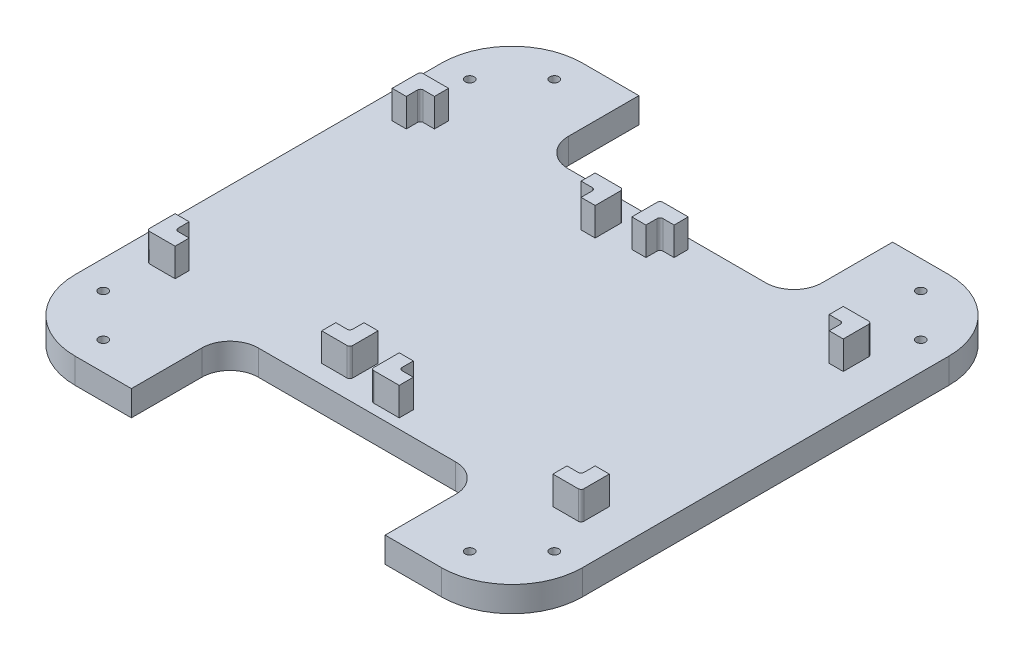
SolidWorks part; units mm, degrees
ref_plane "Front Plane" through (0, 0, 0) normal (0, 0, 1) x (1, 0, 0)
ref_plane "Top Plane" through (0, 0, 0) normal (0, 1, 0) x (1, 0, 0)
ref_plane "Right Plane" through (0, 0, 0) normal (1, 0, 0) x (0, 0, -1)
sketch "Sketch1" plane through (0, 0, 0) normal (0, 1, 0) x (1, 0, 0)
  line L1 (-65, -90) -> (65, -90)
  line L2 (-90, -65) -> (-90, 65)
  line L3 (-65, 90) -> (65, 90)
  line L4 (90, -65) -> (90, 65)
  arc A0 (-90, 65) -> (-65, 90) centre (-65, 65) cw
  arc A1 (65, 90) -> (90, 65) centre (65, 65) cw
  arc A2 (90, -65) -> (65, -90) centre (65, -65) cw
  arc A3 (-65, -90) -> (-90, -65) centre (-65, -65) cw
  point P4 (-90, 0)
  point P6 (0, 90)
  dimension "D3" = 25
  dimension "D1" = 180
  dimension "D2" = 180
extrude "Plate" add sketch "Sketch1" along normal blind 9
sketch "Sketch3" plane through (0, 9, 0) normal (0, 1, 0) x (1, 0, 0)
  line L0 (-65, 90) -> (-65, -90) construction
  line L1 (65, 90) -> (65, -90) construction
  line L2 (-90, 65) -> (90, 65) construction
  line L3 (-90, -65) -> (90, -65) construction
  circle A0 centre (-65, 80) radius 1.6
  circle A1 centre (-80, 65) radius 1.6
  circle A2 centre (80, 65) radius 1.6
  circle A3 centre (80, -65) radius 1.6
  circle A4 centre (65, 80) radius 1.6
  circle A5 centre (65, -80) radius 1.6
  circle A6 centre (-65, -80) radius 1.6
  circle A7 centre (-80, -65) radius 1.6
  dimension "D1" = 3.2
  dimension "D2" = 15
  dimension "D3" = 15
  dimension "D4" = 15
  dimension "D5" = 15
  dimension "D6" = 15
  dimension "D7" = 15
  dimension "D8" = 15
  dimension "D9" = 15
extrude "Hex Holes" cut sketch "Sketch3" against normal through all
sketch "Sketch4" plane through (0, 9, 0) normal (0, 1, 0) x (1, 0, 0)
  line L0 (90, -65) -> (90, 65) construction
  line L1 (-15, -42.5) -> (-15, 42.5) construction
  line L2 (-15, 42.5) -> (-75, 42.5) construction
  line L3 (6, 41.5) -> (6, 46.5)
  line L4 (7, 45.5) -> (70, 45.5) construction
  line L5 (7, 45.5) -> (7, -45.5) construction
  line L6 (7, -45.5) -> (70, -45.5) construction
  line L7 (70, 45.5) -> (70, -45.5) construction
  line L8 (6, 46.5) -> (11, 46.5)
  line L9 (11, 46.5) -> (11, 51.5)
  line L10 (11, 51.5) -> (1, 51.5)
  line L11 (1, 51.5) -> (1, 41.5)
  line L12 (1, 41.5) -> (6, 41.5)
  line L13 (66, 51.5) -> (76, 51.5)
  line L14 (76, 51.5) -> (76, 41.5)
  line L15 (76, 41.5) -> (71, 41.5)
  line L16 (71, 41.5) -> (71, 46.5)
  line L17 (71, 46.5) -> (66, 46.5)
  line L18 (66, 46.5) -> (66, 51.5)
  line L19 (1.5, -41.5) -> (1.5, -51.5)
  line L20 (1.5, -51.5) -> (11.5, -51.5)
  line L21 (11.5, -51.5) -> (11.5, -46.5)
  line L22 (11.5, -46.5) -> (6.5, -46.5)
  line L23 (6.5, -46.5) -> (6.5, -41.5)
  line L24 (6.5, -41.5) -> (1.5, -41.5)
  line L25 (66, -46.5) -> (66, -51.5)
  line L26 (66, -51.5) -> (76, -51.5)
  line L27 (76, -51.5) -> (76, -41.5)
  line L28 (76, -41.5) -> (71, -41.5)
  line L29 (71, -41.5) -> (71, -46.5)
  line L30 (71, -46.5) -> (66, -46.5)
  line L31 (-75, 42.5) -> (-75, -42.5) construction
  line L32 (-90, 0) -> (90, 0) construction
  line L33 (-90, 65) -> (-90, -65) construction
  line L62 (-75, -42.5) -> (-15, -42.5) construction
  line L63 (-76, 43.5) -> (-71, 43.5)
  line L64 (-71, 43.5) -> (-71, 48.5)
  line L65 (-71, 48.5) -> (-81, 48.5)
  line L66 (-81, 48.5) -> (-81, 38.5)
  line L67 (-76, 43.5) -> (-76, 38.5)
  line L68 (-76, 38.5) -> (-81, 38.5)
  line L69 (-19, 43.5) -> (-19, 48.5)
  line L70 (-19, 48.5) -> (-9, 48.5)
  line L71 (-9, 48.5) -> (-9, 38.5)
  line L72 (-9, 38.5) -> (-14, 38.5)
  line L73 (-14, 38.5) -> (-14, 43.5)
  line L74 (-14, 43.5) -> (-19, 43.5)
  line L75 (-76, -38.5) -> (-76, -43.5)
  line L76 (-76, -43.5) -> (-71, -43.5)
  line L77 (-71, -43.5) -> (-71, -48.5)
  line L78 (-71, -48.5) -> (-81, -48.5)
  line L79 (-81, -48.5) -> (-81, -38.5)
  line L80 (-81, -38.5) -> (-76, -38.5)
  line L81 (-19, -43.5) -> (-14, -43.5)
  line L82 (-14, -43.5) -> (-14, -38.5)
  line L83 (-14, -38.5) -> (-9, -38.5)
  line L84 (-9, -38.5) -> (-9, -48.5)
  line L85 (-9, -48.5) -> (-19, -48.5)
  line L86 (-19, -48.5) -> (-19, -43.5)
  point P25 (1, 46.5)
  point P31 (70, 0)
  point P40 (-75, 0)
  point P67 (70, 40.1953)
  dimension "D1" = 91
  dimension "D2" = 63
  dimension "D3" = 85
  dimension "D4" = 1
  dimension "D5" = 1
  dimension "D6" = 5
  dimension "D7" = 1
  dimension "D8" = 1
  dimension "D9" = 1
  dimension "D10" = 1
  dimension "D11" = 1
  dimension "D12" = 20
  dimension "D13" = 60
  dimension "D14" = 15
  dimension "D15" = 5
  dimension "D16" = 1
  dimension "D17" = 1
  dimension "D18" = 1
  dimension "D19" = 1
extrude "Raspberry Pi Holder" add sketch "Sketch4" along normal blind 10
fillet "Fillet1" radius 1 16 edges at (1, 14, -51.5) (6, 14, -46.5) (6.5, 14, 46.5) (1.5, 14, 51.5) (71, 14, 46.5) (76, 14, 51.5) (76, 14, -51.5) (71, 14, -46.5) (-14, 14, 43.5) (-76, 14, 43.5) (-9, 14, 48.5) (-81, 14, 48.5) (-76, 14, -43.5) (-81, 14, -48.5) (-14, 14, -43.5) (-9, 14, -48.5)
sketch "Sketch5" plane through (0, 9, 0) normal (0, 1, 0) x (1, 0, 0)
  line L10 (65, 90) -> (-65, 90) construction
  line L11 (-45, 90) -> (45, 90)
  line L12 (-45, 90) -> (-45, 55)
  line L13 (-45, 55) -> (45, 55)
  line L14 (45, 90) -> (45, 55)
  line L15 (-65, -90) -> (65, -90) construction
  line L16 (-45, -90) -> (45, -90)
  line L17 (-45, -90) -> (-45, -55)
  line L18 (-45, -55) -> (45, -55)
  line L19 (45, -90) -> (45, -55)
  line L20 (0, 90) -> (0, -90) construction
  point P2 (0, 90)
  dimension "D1" = 90
  dimension "D2" = 35
extrude "Cut-Extrude1" cut sketch "Sketch5" against normal through all
fillet "Fillet2" radius 10 4 edges at (45, 4.5, -55) (-45, 4.5, -55) (45, 4.5, 55) (-45, 4.5, 55)
